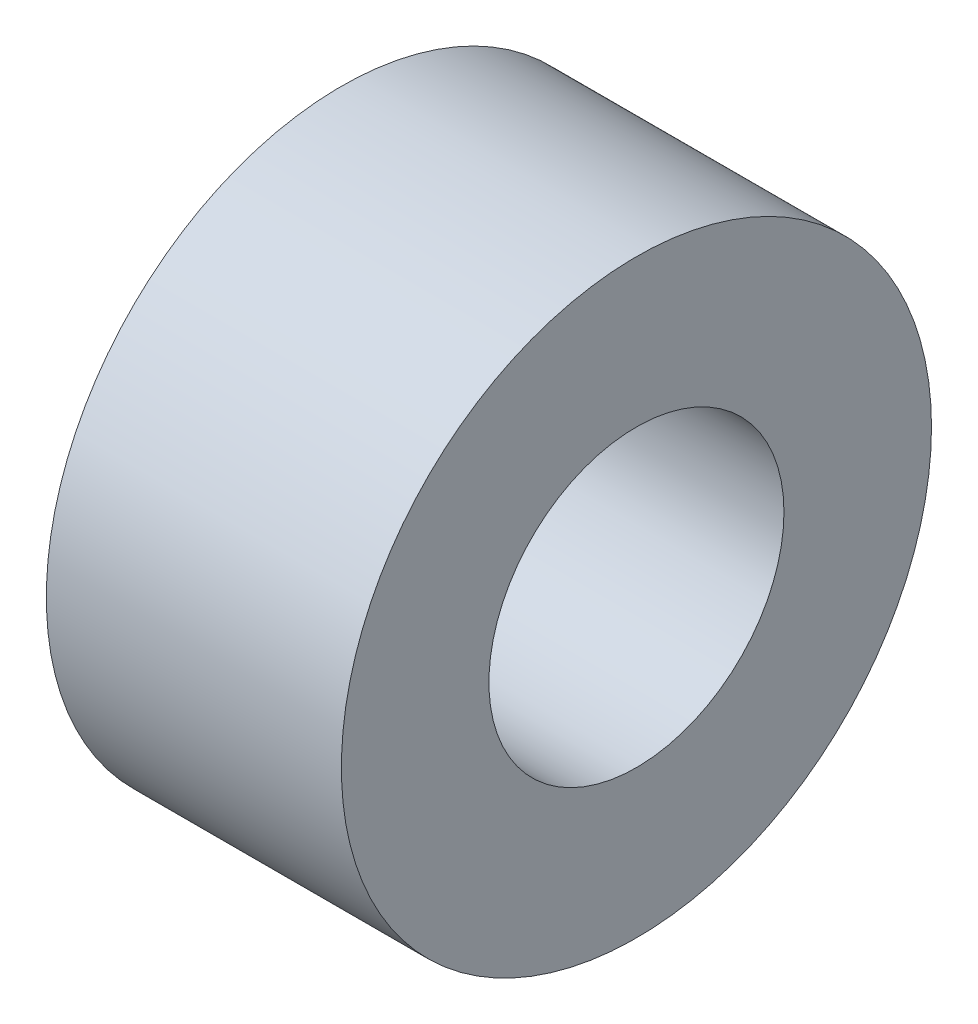
SolidWorks part; units mm, degrees
ref_plane "Front Plane" through (0, 0, 0) normal (0, 0, 1) x (1, 0, 0)
ref_plane "Top Plane" through (0, 0, 0) normal (0, 1, 0) x (1, 0, 0)
ref_plane "Right Plane" through (0, 0, 0) normal (1, 0, 0) x (0, 0, -1)
sketch "Esquisse1" plane through (0, 0, 0) normal (1, 0, 0) x (0, 0, -1)
  circle A0 centre (0, 0) radius 5
  dimension "D1" = 10
extrude "Boss.-Extru.1" add sketch "Esquisse1" along normal blind 2.5 and the other way blind 2.5
ref_plane "Plan1" through (2.5, 0, 0) normal (1, 0, 0) x (0, 0, -1)
sketch "Esquisse2" plane through (2.5, 0, 0) normal (1, 0, 0) x (0, 0, -1)
  circle A0 centre (0, 0) radius 2.5
  dimension "D1" = 5
extrude "Enlèv. mat.-Extru.1" cut sketch "Esquisse2" against normal through all contours A0
